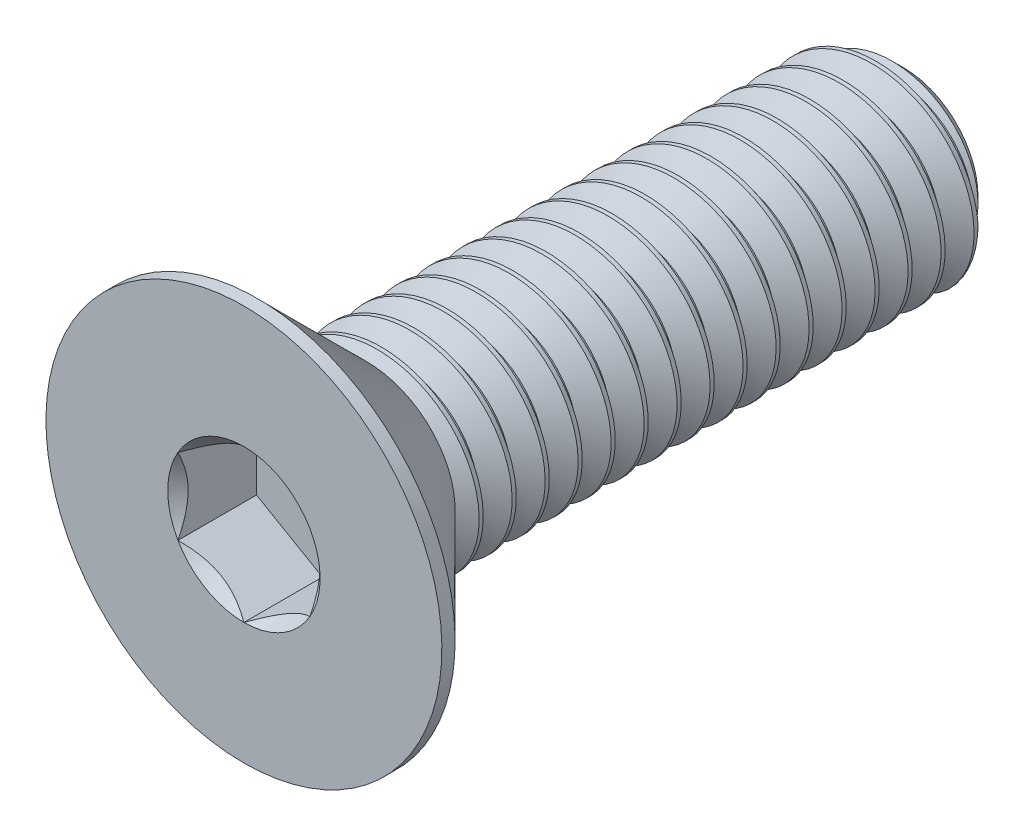
SolidWorks part; units mm, degrees
ref_plane "Front" through (0, 0, 0) normal (0, 0, 1) x (1, 0, 0)
ref_plane "Top" through (0, 0, 0) normal (0, 1, 0) x (1, 0, 0)
ref_plane "Right" through (0, 0, 0) normal (1, 0, 0) x (0, 0, -1)
sketch "Sketch1" plane through (0, 0, 0) normal (1, 0, 0) x (0, 0, -1)
  line L0 (0, 3) -> (0.2, 3) construction
  line L1 (0.2, 3) -> (1.7, 1.5) construction
  line L2 (0, 1.5) -> (10, 1.5)
  line L3 (10, 1.5) -> (10, 0)
  line L4 (10, 0) -> (0, 0)
  line L5 (0, 0) -> (0, 3) construction
  line L6 (0, 3) -> (0, -3) construction
  line L7 (10, 1.5) -> (10, -1.5) construction
  line L8 (0, -3) -> (0.2, -3) construction
  line L9 (0.2, -3) -> (1.7, -1.5) construction
  line L11 (0, 1.5) -> (0, 0)
  line L12 (1.7, 1.5) -> (1.7, 0) construction
revolve "Revolve1" add sketch "Sketch1" angle 360 mid plane about L4
sketch "Sketch3" plane through (0, 0, -10) normal (0, 0, -1) x (-1, 0, 0)
  circle A0 centre (0, 0) radius 1.5
curve "Helix/Spiral1" pitch 0.5 height 10 radius 1.5 centre (0, 0, -10) axis (0, 0, 1) start towards (0, 1, 0)
sketch "Sketch2" plane through (0, 0, 0) normal (1, 0, 0) x (0, 0, -1)
  line L0 (10, 1.5) -> (10.4375, 1.5)
  line L1 (10.4375, 1.5) -> (10.25, 1.1752)
  line L2 (10.25, 1.1752) -> (10.1875, 1.1752)
  line L3 (10.1875, 1.1752) -> (10, 1.5)
  line L4 (10.0938, 1.3376) -> (10.3438, 1.3376) construction
  dimension "D1" = 60
  dimension "D2" = 0.0625
  dimension "D3" = 0.25
chamfer "Chamfer1" distance 0.375 angle 45 1 edges at (0, 1.5, -10)
sweep "Cut-Sweep1" cut profiles "Sketch2" path "Helix/Spiral1" align with end faces yes
sketch "Sketch7" plane through (0, 0, 0) normal (1, 0, 0) x (0, 0, -1)
  line L0 (0, 3) -> (0.2, 3) construction
  line L1 (0.2, 3) -> (1.7, 1.5) construction
  line L2 (0, 3) -> (0.2, 3)
  line L3 (0.2, 3) -> (1.7, 1.5)
  line L4 (1.7, 1.5) -> (1.7, 0) construction
  line L5 (1.7, 1.5) -> (1.7, 0)
  line L7 (0, 0) -> (0, 3) construction
  line L8 (0, 0) -> (0, 3)
  line L9 (0, 0) -> (1.7, 0)
  line L10 (3.3, 0) -> (-3.3, 0) construction
revolve "Revolve2" add sketch "Sketch7" angle 360 mid plane about L9
ref_plane "Plane1" through (0, 0, -1.7) normal (0, 0, 1) x (1, 0, 0)
sketch "Sketch8" plane through (0, 0, -1.7) normal (0, 0, 1) x (1, 0, 0)
  circle A0 centre (0, 0) radius 1.5
extrude "Boss-Extrude1" add sketch "Sketch8" against normal through all draft 45
sketch "Sketch5" plane through (0, 0, 0) normal (0, 0, 1) x (1, 0, 0)
  line L1 (1, -0.5774) -> (1, 0.5774)
  line L2 (1, 0.5774) -> (0, 1.1547)
  line L3 (0, 1.1547) -> (-1, 0.5774)
  line L4 (-1, 0.5774) -> (-1, -0.5774)
  line L5 (-1, -0.5774) -> (0, -1.1547)
  line L6 (0, -1.1547) -> (1, -0.5774)
  circle A0 centre (0, 0) radius 1 construction
  dimension "Hex" = 2
extrude "Cut-Extrude2" cut sketch "Sketch5" against normal blind 1.19
sketch "Sketch6" plane through (0, 0, 0) normal (0, 0, 1) x (1, 0, 0)
  circle A0 centre (0, 0) radius 1.1547
extrude "Cut-Extrude3" cut sketch "Sketch6" against normal blind 1.19 draft 45
sketch "Sketch9" [suppressed] plane through (0, 0, -1.5) normal (0, 0, 1) x (1, 0, 0)
  circle A1 centre (0, 0) radius 1.25
  circle A2 centre (0, 0) radius 1.25
  point P0 (0, 1.25)
  dimension "D1" = 0
extrude "Boss-Extrude2" [suppressed] add sketch "Sketch9" against normal offset from surface (3.5 mm away) 26 up to face at (0, 1.125, -10)
fillet "Fillet1" [suppressed] radius 0.3
sketch "Sketch10" plane through (0, 0, 0) normal (1, 0, 0) x (0, 0, -1)
  line L0 (10, 1.5) -> (10, -1.5) construction
  point P0 (9.25, -1.5)
  dimension "D1" = 0.75
equation "\"D3@Helix/Spiral1\" = \"Lg@Sketch1\""
equation "\"D2@Sketch2\" = \"D4@Helix/Spiral1\" * .125"
equation "\"D3@Sketch2\" = \"D4@Helix/Spiral1\" * .5"
equation "\"D1@Chamfer1\" = \"D4@Helix/Spiral1\" * .75"
equation "\"D1@Cut-Extrude2\" = \"Head Ht@Sketch1\" * .7"
equation "\"D1@Sketch10\" = \"D4@Helix/Spiral1\" * 1.5"
equation "\"D1@Cut-Extrude3\" = \"D1@Cut-Extrude2\""
equation "\"D1@Fillet1\" = \"Dia@Sketch1\" * .1"
